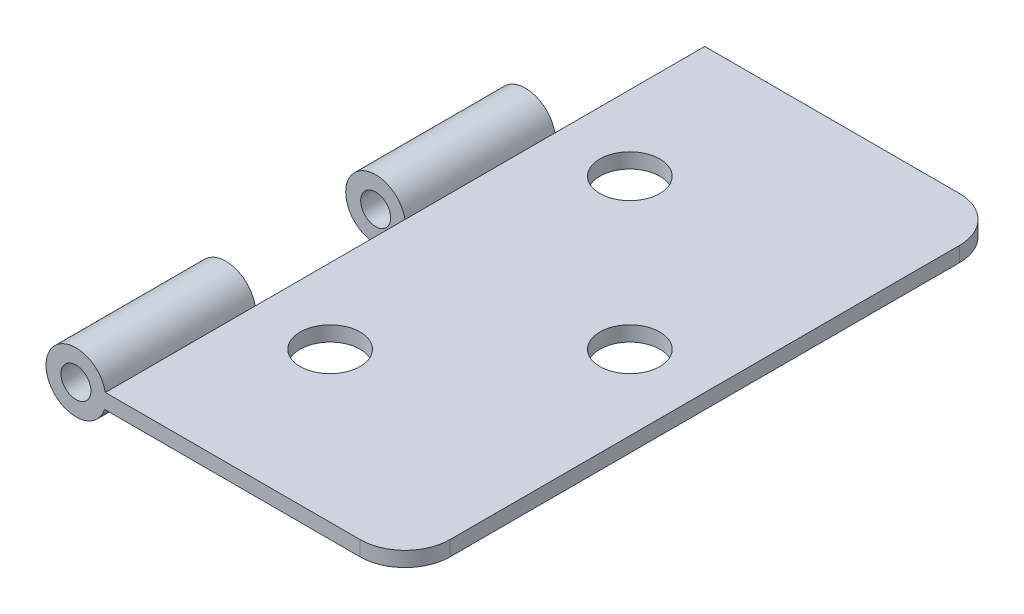
SolidWorks part; units mm, degrees
ref_plane "Front Plane" through (0, 0, 0) normal (0, 0, 1) x (1, 0, 0)
ref_plane "Top Plane" through (0, 0, 0) normal (0, 1, 0) x (1, 0, 0)
ref_plane "Right Plane" through (0, 0, 0) normal (1, 0, 0) x (0, 0, -1)
sketch "Sketch3" plane through (0, 0, 0) normal (0, 0, 1) x (1, 0, 0)
  line L1 (14.1079, 1) -> (14.1079, 0)
  line L2 (14.1079, 0) -> (-5.948, 0)
  line L3 (-5.8921, 1) -> (14.1079, 1)
  circle A1 centre (-7.8533, 0.608) radius 1
  circle A2 centre (-7.8533, 0.608) radius 2
  dimension "D1" = 20
  dimension "D3" = 2
  dimension "D4" = 4
  dimension "D2" = 1
extrude "Boss-Extrude2" add sketch "Sketch3" against normal blind 40 contours A2 L2 L1 L3 region at (4.1153, 0.4998, 0)
extrude "Boss-Extrude3" add sketch "Sketch3<4>" against normal blind 10 contours A2 A1 region at (-5.9193, 0.7994, 0)
sketch "Sketch3<4>" plane through (0, 0, 0) normal (0, 0, 1) x (1, 0, 0) same geometry as "Sketch3"
extrude "Boss-Extrude4" add sketch "Sketch3<5>" against normal blind 10 from offset 20 contours A2 A1 region at (-5.9193, 0.7994, 0) offset against normal yes
sketch "Sketch3<5>" plane through (0, 0, 0) normal (0, 0, 1) x (1, 0, 0) same geometry as "Sketch3"
sketch "Sketch5" plane through (0, 1, 0) normal (0, 1, 0) x (1, 0, 0)
  line L0 (14.1079, 40) -> (14.1079, 0) construction
  circle A0 centre (-0.8921, 30) radius 2
  circle A1 centre (-0.8921, 10) radius 2
  circle A2 centre (9.1079, 20) radius 2
  point P6 (0, 0)
  dimension "D1" = 4
  dimension "D4" = 10
  dimension "D5" = 5
  dimension "D2" = 5
  dimension "D3" = 5
extrude "Cut-Extrude1" cut sketch "Sketch5" against normal blind 10
fillet "Fillet1" radius 3 1 edges at (14.1079, 0.5, -40)
fillet "Fillet2" radius 3 1 edges at (14.1079, 0.5, 0)
